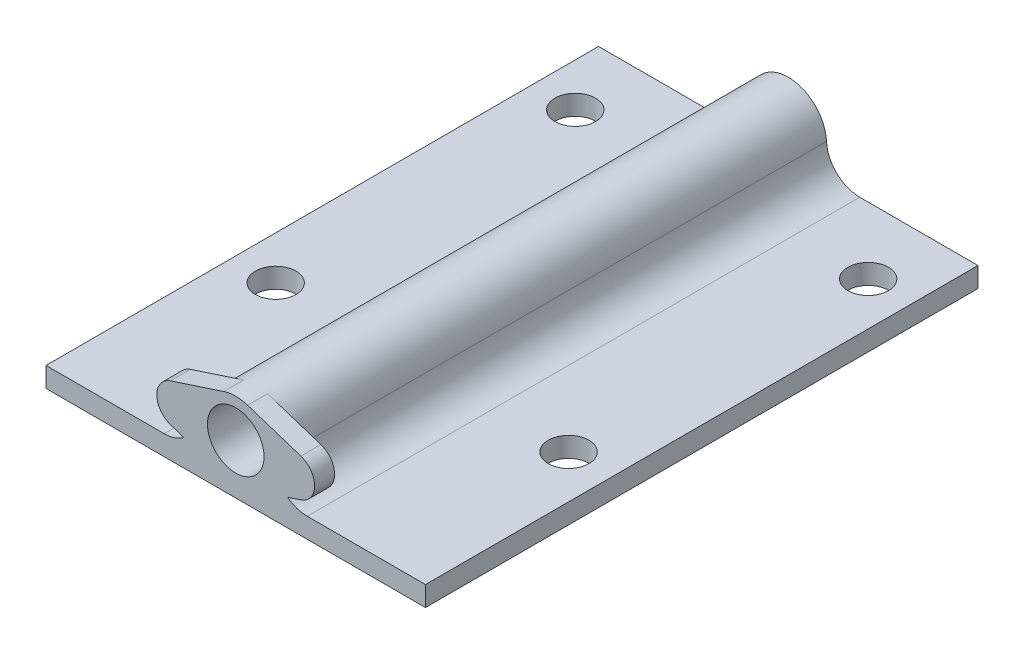
SolidWorks part; units mm, degrees
note: The reader was unsure of these and kept them because the rebuilt part matched: shared geometry of "Esquisse1<2>".
ref_plane "Plan de face" through (0, 0, 0) normal (0, 0, 1) x (1, 0, 0)
ref_plane "Plan de dessus" through (0, 0, 0) normal (0, 1, 0) x (1, 0, 0)
ref_plane "Plan de droite" through (0, 0, 0) normal (1, 0, 0) x (0, 0, -1)
sketch "Esquisse1" plane through (0, 0, 0) normal (0, 0, 1) x (1, 0, 0)
  line L0 (-5, 4.25) -> (5, -4.25) construction
  line L1 (-5, 4.25) -> (5, 4.25) construction
  line L2 (-5, 4.25) -> (-5, -4.25) construction
  line L3 (-5, -4.25) -> (5, -4.25) construction
  line L4 (5, 4.25) -> (5, -4.25) construction
  circle A0 centre (0, 0) radius 4.25
  point P7 (0, 0)
  point P8 (0, 4.25)
  dimension "D1" = 8.5
  dimension "D2" = 8.5
  dimension "D3" = 10
extrude "Boss.-Extru.1" add sketch "Esquisse1" along normal blind 1.5
extrude "Extru.-Mince1" add sketch "Esquisse1<2>" along normal blind 80 thin contours A0
sketch "Esquisse1<2>" plane through (0, 0, 0) normal (0, 0, 1) x (1, 0, 0) same geometry as "Esquisse1"
sketch "Esquisse2" plane through (0, 0, 80) normal (0, 0, 1) x (1, 0, 0)
  line L0 (-1.7859, 5.4656) -> (-9.7859, 2.8516)
  line L1 (-4.25, 0) -> (4.25, 0) construction
  line L6 (0, -5.75) -> (0, 5.75) construction
  line L8 (-1.7859, -5.4656) -> (-9.7859, -2.8516)
  line L9 (1.7859, -5.4656) -> (9.7859, -2.8516)
  line L10 (1.7859, 5.4656) -> (9.7859, 2.8516)
  circle A0 centre (0, 0) radius 5.75 construction
  arc A1 (-9.7859, 2.8516) -> (-11.8541, 0) centre (-8.8541, 0) ccw
  arc A2 (-9.7859, -2.8516) -> (-11.8541, 0) centre (-8.8541, 0) cw
  arc A3 (9.7859, -2.8516) -> (11.8541, 0) centre (8.8541, 0) ccw
  arc A4 (9.7859, 2.8516) -> (11.8541, 0) centre (8.8541, 0) cw
  circle A5 centre (0, 0) radius 4.25 construction
  circle A6 centre (0, 0) radius 4.25
  circle A7 centre (0, 0) radius 5.75
  circle A8 centre (0, 0) radius 4.25 construction
  point P6 (-4.25, 0)
  point P8 (4.25, 0)
  point P11 (0, -5.75)
  point P14 (0, 5.75)
  circle M5 centre (0, 0) radius 5.75
  circle M6 centre (0, 0) radius 4.25
  dimension "D1" = 8
  dimension "D2" = 3
extrude "Boss.-Extru.2" add sketch "Esquisse2" along normal blind 3 contours A4 L10 L9 A3 M5 | A2 L8 L0 A1 M5 | M5 M6 | A6
sketch "Esquisse3" plane through (0, 0, 0) normal (0, 1, 0) x (1, 0, 0)
  line L1 (-10.75, -20) -> (10.75, -20)
  line L2 (-10.75, -20) -> (-10.75, -25)
  line L3 (-10.75, -25) -> (10.75, -25)
  line L4 (10.75, -20) -> (10.75, -25)
  line L6 (5.75, 0) -> (-5.75, 0) construction
  line L7 (-10.75, -55) -> (10.75, -55)
  line L8 (-10.75, -50) -> (10.75, -50)
  line L9 (-10.75, -50) -> (-10.75, -55)
  line L10 (10.75, -50) -> (10.75, -55)
  line L11 (-10.75, -85) -> (10.75, -85)
  line L12 (-10.75, -80) -> (10.75, -80)
  line L13 (-10.75, -80) -> (-10.75, -85)
  line L14 (10.75, -80) -> (10.75, -85)
  line L15 (-10.75, -115) -> (10.75, -115)
  line L16 (-10.75, -110) -> (10.75, -110)
  line L17 (-10.75, -110) -> (-10.75, -115)
  line L18 (10.75, -110) -> (10.75, -115)
  line L19 (-10.75, -20) -> (10.75, -25) construction
  point P4 (0, -22.5)
  point P11 (0, -20)
  dimension "D1" = 5
  dimension "D2" = 20
  dimension "D4" = 30
  dimension "D5" = 21.5
  dimension "D3" = 4
ref_plane "Plan1" through (0, -4.5, 0) normal (0, 1, 0) x (1, 0, 0)
sketch "Esquisse4" plane through (0, -4.5, 0) normal (0, 1, 0) x (1, 0, 0)
  line L0 (5.75, 0) -> (-5.75, 0) construction
  line L1 (-28.5, 0) -> (28.5, 0)
  line L2 (-28.5, 0) -> (-28.5, -110)
  line L3 (-28.5, -110) -> (28.5, -110)
  line L4 (0, 0) -> (0, -110)
  line L5 (0, 0) -> (0, -169.7294) construction
  line L6 (28.5, 0) -> (28.5, -110)
  line L7 (1.7859, -83) -> (9.7859, -83) construction
  line L8 (-28.5, -58) -> (28.5, -58)
  line L9 (-28.5, -58) -> (-28.5, -83)
  line L10 (-28.5, -83) -> (28.5, -83)
  line L11 (28.5, -58) -> (28.5, -83)
  circle A0 centre (-22, -10) radius 3.05
  circle A1 centre (-22, -55) radius 3.05
  circle A2 centre (-22, -100) radius 3.05
  circle A3 centre (22, -100) radius 3.05
  circle A4 centre (22, -10) radius 3.05
  circle A5 centre (22, -55) radius 3.05
  point P19 (22, -55)
  point P31 (0, -58)
  dimension "D3" = 6.1
  dimension "D4" = 6.5
  dimension "D5" = 10
  dimension "D7" = 45
  dimension "D1" = 110
  dimension "D2" = 28.5
  dimension "D8" = 25
  dimension "D6" = 3
extrude "Boss.-Extru.3" add sketch "Esquisse4" against normal blind 3 contours L6 L1 L4 L3 A3 A4 | L4 L1 L2 L3 A2 A1 A0 | L5 L8 L9 L10 | L8 L5 L10 L11
fillet "Congé1" radius 5 2 edges at (3.5795, -4.5, 40) (-3.5795, -4.5, 40)
